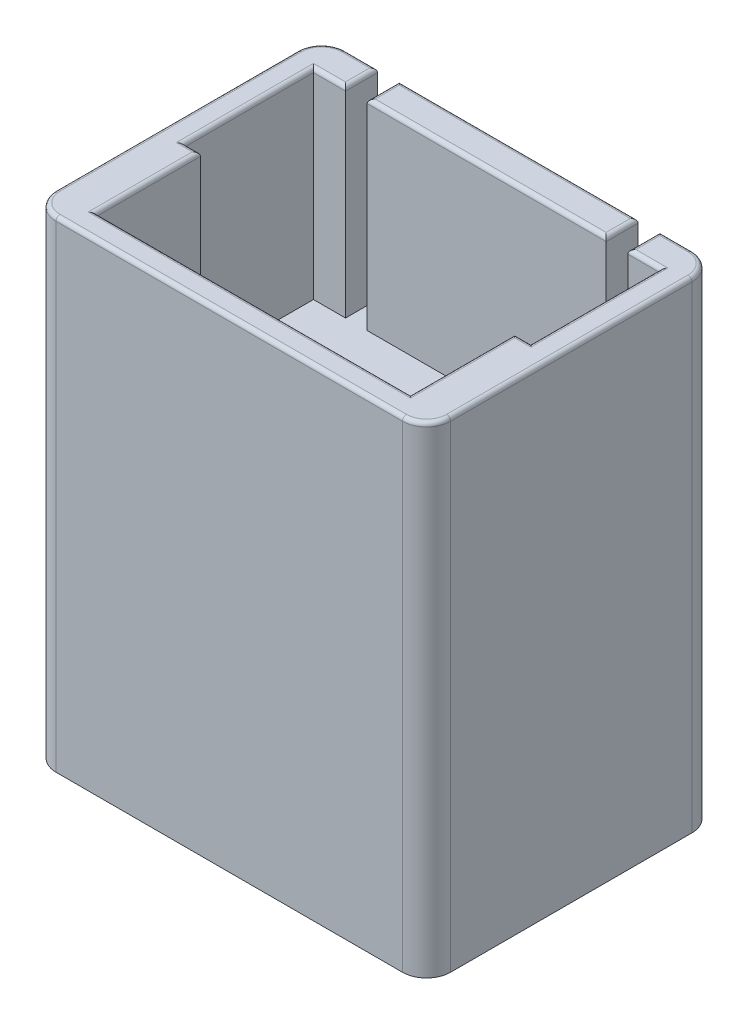
SolidWorks part; units mm, degrees
material "二氧化硅"
ref_plane "前视基准面" through (0, 0, 0) normal (0, 0, 1) x (1, 0, 0)
ref_plane "上视基准面" through (0, 0, 0) normal (0, 1, 0) x (1, 0, 0)
ref_plane "右视基准面" through (0, 0, 0) normal (1, 0, 0) x (0, 0, -1)
other "Configuration Table"
sketch "草图1" plane through (0, 0, 0) normal (0, 1, 0) x (1, 0, 0)
  line L1 (-21.6, 8) -> (21.6, 8)
  line L2 (-21.6, 8) -> (-21.6, -8.1)
  line L3 (-21.6, -8.1) -> (21.6, -8.1)
  line L4 (21.6, 8) -> (21.6, -8.1)
  line L5 (-17.6, 8) -> (-14.9, 8)
  line L6 (-17.6, 8) -> (-17.6, 12)
  line L7 (-17.6, 12) -> (-14.9, 12)
  line L8 (-14.9, 8) -> (-14.9, 12)
  line L9 (14.9, 8) -> (17.6, 8)
  line L10 (14.9, 8) -> (14.9, 12)
  line L11 (14.9, 12) -> (17.6, 12)
  line L12 (17.6, 8) -> (17.6, 12)
  line L13 (-19.6, -8.1) -> (19.6, -8.1)
  line L14 (-19.6, -8.1) -> (-19.6, -21.1)
  line L15 (-19.6, -21.1) -> (19.6, -21.1)
  line L16 (19.6, -8.1) -> (19.6, -21.1)
  line L17 (-24.6, 12) -> (24.6, 12)
  line L18 (-24.6, 12) -> (-24.6, -24.1)
  line L19 (-24.6, -24.1) -> (24.6, -24.1)
  line L20 (24.6, 12) -> (24.6, -24.1)
  dimension "D1" = 16.1
  dimension "D2" = 43.2
  dimension "D3" = 21.6
  dimension "D4" = 8
  dimension "D5" = 2
  dimension "D6" = 2
  dimension "D7" = 13
  dimension "D8" = 4
  dimension "D9" = 4
  dimension "D10" = 4
  dimension "D11" = 2.7
  dimension "D12" = 4
  dimension "D13" = 2.7
  dimension "D14" = 0
  dimension "D15" = 3
  dimension "D16" = 3
  dimension "D17" = 3
extrude "凸台-拉伸1" add sketch "草图1" along normal blind 25 contours L20 L17 L12 L1 L4 L3 L16 L15 L14 L2 L6 L18 L19 | L17 L8 L1 L10 region at (-22.2102, 0, 0.05) region at (0, 0, -10)
sketch "草图2" plane through (0, 0, 0) normal (0, -1, 0) x (1, 0, 0)
  line L1 (-24.6, -12) -> (24.6, -12)
  line L2 (-24.6, -12) -> (-24.6, 24.1)
  line L3 (-24.6, 24.1) -> (24.6, 24.1)
  line L4 (24.6, -12) -> (24.6, 24.1)
extrude "凸台-拉伸2" add sketch "草图2" along normal blind 5
sketch "草图4" plane through (0, 0, 21.1) normal (0, 0, -1) x (-1, 0, 0)
  line L0 (19.6, 0) -> (-19.6, 0) construction
  line L1 (-3.0803, 0) -> (2.9197, 0)
  line L2 (-3.0803, 0) -> (-3.0803, 6)
  line L3 (-3.0803, 6) -> (2.9197, 6)
  line L4 (2.9197, 0) -> (2.9197, 6)
  dimension "D1" = 6
  dimension "D2" = 6
extrude "切除-拉伸1" cut sketch "草图4" against normal blind 1.5
sketch "草图5" plane through (0, 0, 0) normal (0, 1, 0) x (1, 0, 0)
  line L1 (-2.9197, -21.1) -> (3.0803, -21.1)
  line L2 (-2.9197, -21.1) -> (-2.9197, -8.1)
  line L3 (-2.9197, -8.1) -> (3.0803, -8.1)
  line L4 (3.0803, -21.1) -> (3.0803, -8.1)
  dimension "D1" = 6
  dimension "D2" = 13
extrude "切除-拉伸2" cut sketch "草图5" against normal blind 5.5
sketch "草图6" plane through (0, 0, 0) normal (0, 1, 0) x (1, 0, 0)
  line L0 (21.6, 8) -> (21.6, -8.1) construction
  line L1 (-0.4, -5.5854) -> (19.6, -5.5854)
  line L2 (-0.4, -5.5854) -> (-0.4, 4.4146)
  line L3 (-0.4, 4.4146) -> (19.6, 4.4146)
  line L4 (19.6, -5.5854) -> (19.6, 4.4146)
  dimension "D1" = 20
  dimension "D2" = 10
  dimension "D3" = 22
extrude "切除-拉伸3" cut sketch "草图6" against normal blind 5.5
sketch "草图8" plane through (0, -5, 0) normal (0, -1, 0) x (1, 0, 0)
  line L0 (-24.6, 24.1) -> (24.6, 24.1)
  line L1 (24.6, 24.1) -> (-24.6, 24.1) construction
  line L2 (24.6, -12) -> (24.6, 24.1) construction
sketch "草图9" plane through (0, -5, 0) normal (0, -1, 0) x (1, 0, 0)
  line L1 (-24.6, 24.1) -> (24.6, 24.1)
  line L2 (-24.6, 24.1) -> (-24.6, -12)
  line L3 (-24.6, -12) -> (24.6, -12)
  line L4 (24.6, 24.1) -> (24.6, -12)
sketch "草图10" plane through (0, 0, 0) normal (0, 1, 0) x (1, 0, 0)
  line L1 (-2.9197, -21.1) -> (3.1167, -21.1)
  line L2 (-2.9197, -21.1) -> (-2.9197, -22.6)
  line L3 (-2.9197, -22.6) -> (3.1167, -22.6)
  line L4 (3.1167, -21.1) -> (3.1167, -22.6)
  dimension "D1" = 6.0364
  dimension "D2" = 1.5
sketch "草图11" plane through (0, 0, 0) normal (0, 1, 0) x (1, 0, 0)
  line L1 (3.1167, -22.6) -> (-2.9197, -22.6)
  line L2 (3.1167, -22.6) -> (3.1167, -8.1)
  line L3 (3.1167, -8.1) -> (-2.9197, -8.1)
  line L4 (-2.9197, -22.6) -> (-2.9197, -8.1)
extrude "切除-拉伸10" cut sketch "草图11" against normal blind 38
sketch "草图12" plane through (0, -5, 0) normal (0, -1, 0) x (1, 0, 0)
  line L1 (-24.6, 24.1) -> (24.6, 24.1)
  line L2 (-24.6, 24.1) -> (-24.6, -12)
  line L3 (-24.6, -12) -> (24.6, -12)
  line L4 (24.6, 24.1) -> (24.6, -12)
  line L5 (-2.9197, 22.6) -> (3.1167, 22.6)
  line L6 (-2.9197, 22.6) -> (-2.9197, 8.1)
  line L7 (-2.9197, 8.1) -> (3.1167, 8.1)
  line L8 (3.1167, 22.6) -> (3.1167, 8.1)
  line L9 (19.6, -4.4146) -> (-0.4, -4.4146)
  line L10 (19.6, -4.4146) -> (19.6, 5.5854)
  line L11 (19.6, 5.5854) -> (-0.4, 5.5854)
  line L12 (-0.4, -4.4146) -> (-0.4, 5.5854)
extrude "凸台-拉伸3" add sketch "草图12" along normal blind 30 contours L2 L1 L4 L3 | L10 L9 L12 L11 | L6 L5 L8 L7
sketch "草图13" plane through (0, -35, 0) normal (0, -1, 0) x (1, 0, 0)
  line L0 (-0.4, -4.4146) -> (-0.4, 5.5854) construction
  line L1 (-0.4, -1.4146) -> (19.6, -1.4146)
  line L2 (-0.4, -1.4146) -> (-0.4, -4.4146)
  line L3 (-0.4, -4.4146) -> (19.6, -4.4146)
  line L4 (19.6, -1.4146) -> (19.6, -4.4146)
  dimension "D1" = 3
extrude "凸台-拉伸4" add sketch "草图13" against normal blind 3
sketch "草图14" plane through (0, -35, 0) normal (0, -1, 0) x (1, 0, 0)
  line L1 (4, -3.9206) -> (-4, -3.9206)
  line L2 (4, -3.9206) -> (4, 3.9206)
  line L3 (4, 3.9206) -> (-4, 3.9206)
  line L4 (-4, -3.9206) -> (-4, 3.9206)
  line L5 (4, -3.9206) -> (-4, 3.9206) construction
  line L6 (4, 3.9206) -> (-4, -3.9206) construction
  point P0 (0, 0)
  dimension "D1" = 8
extrude "切除-拉伸11" cut sketch "草图14" against normal blind 20
fillet "圆角1" radius 3 4 edges at (24.6, -5, -12) (24.6, -5, 24.1) (-24.6, -5, 24.1) (-24.6, -5, -12)
fillet "圆角2" radius 0.5 24 edges at (23.7213, 25, 23.2213) (0, 25, 24.1) (-23.7213, 25, 23.2213) (-24.6, 25, 6.05) (-23.7213, 25, -11.1213) (-19.6, 25, -12) (-17.6, 25, -10) (-19.6, 25, -8) (-21.6, 25, 0.05) (-20.6, 25, 8.1) (-19.6, 25, 14.6) (0, 25, 21.1) (19.6, 25, 14.6) (20.6, 25, 8.1) (21.6, 25, 0.05) (19.6, 25, -8) (17.6, 25, -10) (19.6, 25, -12) (23.7213, 25, -11.1213) (24.6, 25, 6.05) (-14.9, 25, -10) (14.9, 25, -10) (0, 25, -8) (0, 25, -12)
